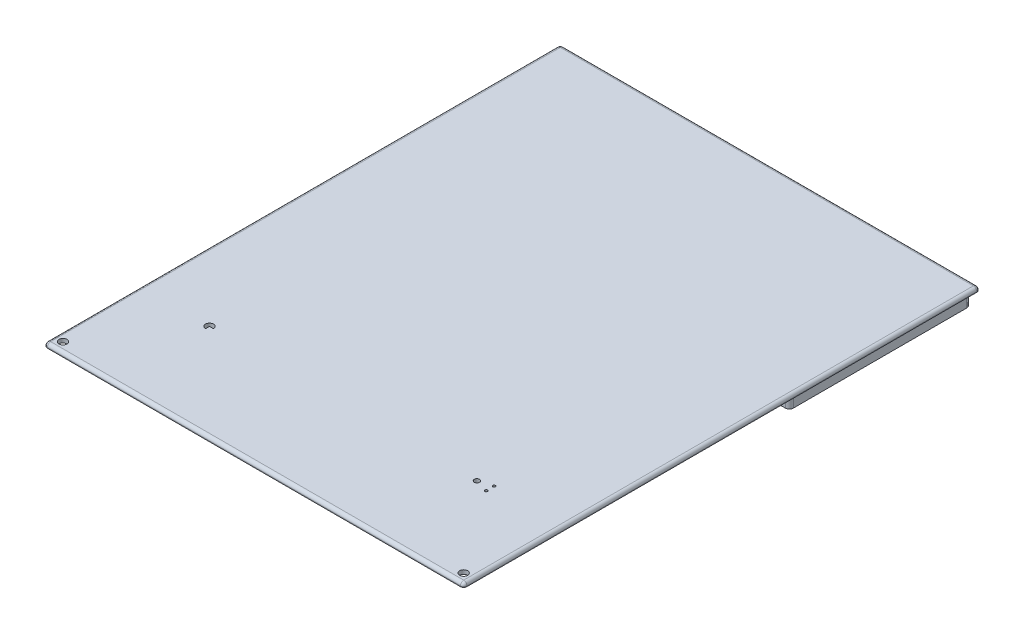
SolidWorks part; units mm, degrees
ref_plane "Front Plane" through (0, 0, 0) normal (0, 0, 1) x (1, 0, 0)
ref_plane "Top Plane" through (0, 0, 0) normal (0, 1, 0) x (1, 0, 0)
ref_plane "Right Plane" through (0, 0, 0) normal (1, 0, 0) x (0, 0, -1)
sketch "Sketch1" plane through (0, 0, 0) normal (0, 1, 0) x (1, 0, 0)
  line L0 (79.25, -36) -> (79.25, 36)
  line L1 (-78, -34.75) -> (78, -34.75)
  line L2 (-78, -34.75) -> (-78, 34.75)
  line L3 (-78, 34.75) -> (78, 34.75)
  line L4 (78, -34.75) -> (78, 34.75)
  line L5 (-78, -34.75) -> (78, 34.75) construction
  line L6 (-78, 34.75) -> (78, -34.75) construction
  line L7 (-79.25, 36) -> (79.25, 36)
  line L8 (-79.25, -36) -> (-79.25, 36)
  line L9 (-78, -36) -> (78, -36)
  line L10 (-78, -36) -> (-78, -86)
  line L11 (-78, -36) -> (78, -36)
  line L12 (-79.25, -36) -> (-79.25, -86)
  line L13 (-79.25, -86) -> (-79.25, -159)
  line L14 (79.25, -36) -> (79.25, -86)
  line L15 (78, -36) -> (78, -86)
  line L16 (-79.25, -36) -> (79.25, -36) construction
  line L17 (-78, -86) -> (-78, -100.5886)
  line L18 (79.25, -86) -> (79.25, -159)
  line L19 (78, -86) -> (78, -157.75)
  line L20 (79.25, -159) -> (-79.25, -159)
  line L21 (78, -159) -> (79.25, -159)
  line L22 (-78, -100.5886) -> (-78, -157.75)
  line L23 (-78, -157.75) -> (78, -157.75)
  line L24 (-78, -157.75) -> (78, -157.75) construction
  line L25 (0, -157.75) -> (0, -117.25)
  line L26 (-40, -117.25) -> (40, -117.25)
  line L27 (-34, -117.25) -> (34, -117.25)
  line L28 (-40, -117.25) -> (-34, -117.25) construction
  circle A0 centre (-37, -117.25) radius 3
  point P0 (0, 0)
  point P27 (0, -117.25)
  point P30 (0, -117.25)
  dimension "D1" = 156
  dimension "D2" = 69.5
  dimension "D4" = 50
  dimension "D5" = 195
  dimension "D6" = 1.25
  dimension "D7" = 40.5
  dimension "D8" = 80
  dimension "D9" = 68
  dimension "D3" = 1.25
sketch "Sketch2" plane through (0, 0, 0) normal (0, 1, 0) x (1, 0, 0)
  line L0 (-79.25, 36) -> (79.25, 36)
  line L1 (79.25, 36) -> (79.25, -159)
  line L2 (79.25, -159) -> (-79.25, -159)
  line L3 (-79.25, -159) -> (-79.25, 36)
extrude "Boss-Extrude1" add sketch "Sketch2" against normal blind 1.25
extrude "Boss-Extrude2" add sketch "Sketch1" along normal blind 105 contours L20 L18 L14 L0 L7 L8 L12 L13 L23 L22 L17 L10 L9 L15 L19 L4 L1 L2 L3 region at (78.9987, 0, 61)
sketch "Sketch4" plane through (0, 0, 0) normal (0, 1, 0) x (1, 0, 0)
  line L0 (-78, -157.75) -> (78, -157.75) construction
  line L1 (0, -157.75) -> (0, -117.75)
  line L2 (0, -5.0875) -> (0, 5.0875) construction
  line L3 (-34, -117.75) -> (34, -117.75)
  line L4 (-40.15, -117.75) -> (-39.575, -117.75)
  line L5 (-40.15, -117.75) -> (-39.575, -117.75) construction
  line L6 (34, -117.75) -> (34.575, -117.75) construction
  line L7 (-34.575, -117.75) -> (34.575, -117.75)
  line L8 (-34.575, -117.75) -> (-34, -117.75) construction
  line L9 (39.575, -117.75) -> (40.15, -117.75) construction
  line L10 (39.575, -117.75) -> (40.15, -117.75)
  circle A0 centre (-37.075, -117.75) radius 2.5
  circle A1 centre (37.075, -117.75) radius 2.5
  point P12 (0, -117.75)
  point P15 (0, -117.75)
  dimension "D1" = 40
  dimension "D2" = 68
  dimension "D3" = 80.3
extrude "Boss-Extrude3" add sketch "Sketch4" along normal blind 8 contours A0 | A1 region at (37.075, 0, 117.75) region at (-37.075, 0, 117.75)
fillet "Fillet2" radius 2 18 edges at (-78, 0, 0) (0, 0, -34.75) (78, 0, 0) (0, 0, 34.75) (0, 0, 36) (78, 0, 96.875) (0, 0, 157.75) (-78, 0, 96.875) (-37.075, 0, 115.25) (37.075, 0, 115.25) (78, 52.5, -34.75) (-78, 52.5, -34.75) (78, 52.5, 34.75) (-78, 52.5, 34.75) (-78, 52.5, 157.75) (78, 52.5, 157.75) (78, 52.5, 36) (-78, 52.5, 36)
sketch "Sketch5" plane through (0, 0, 36) normal (0, 0, 1) x (1, 0, 0)
  line L0 (-76, 105) -> (76, 105) construction
  line L2 (-76, 105) -> (-76, 2) construction
  line L3 (-58.75, 4.5) -> (58.75, 4.5)
  line L4 (-58.75, 4.5) -> (-58.75, 101.5)
  line L5 (-58.75, 101.5) -> (58.75, 101.5)
  line L6 (58.75, 4.5) -> (58.75, 101.5)
  line L7 (-58.75, 53) -> (58.75, 53)
  line L8 (-53.75, 101.5) -> (-53.75, 98)
  line L14 (-58.75, 98) -> (-53.75, 98)
  line L15 (0, 53) -> (0, 77.907)
  circle A0 centre (-53.75, 98) radius 1.55
  circle A1 centre (-53.75, 8) radius 1.55
  circle A2 centre (53.75, 8) radius 1.55
  circle A3 centre (53.75, 98) radius 1.55
  point P8 (0, 53.5)
  dimension "D1" = 97
  dimension "D2" = 117.5
  dimension "D3" = 17.25
  dimension "D4" = 3.5
  dimension "D5" = 5
  dimension "D6" = 3.5
extrude "Cut-Extrude1" cut sketch "Sketch5" against normal blind 8 contours L14 A0 L8 | L8 A0 L14 | A3 | A1 | A2 region at (-54.4078, 98.6578, 36) region at (-53.5307, 97.7807, 36) region at (-53.75, 8, 36) region at (53.75, 98, 36)
sketch "Sketch6" plane through (0, 0, 157.75) normal (0, 0, -1) x (-1, 0, 0)
  line L0 (-76, 2) -> (76, 2) construction
  line L1 (0, 2) -> (0, 22)
  line L2 (0, 5.0875) -> (0, -5.0875) construction
  circle A0 centre (0, 22) radius 8.25
  dimension "D1" = 20
extrude "Cut-Extrude2" cut sketch "Sketch6" against normal blind 8 contours A0 region at (-5.6686, 16.3314, 157.75)
sketch "Sketch8" plane through (-79.25, 0, 0) normal (-1, 0, 0) x (0, 0, 1)
  line L0 (159, 55) -> (116.5, 55)
  line L1 (159, -1.25) -> (159, 105) construction
  line L2 (116.5, 5) -> (116.5, 105)
  line L3 (159, 105) -> (-36, 105) construction
  line L4 (116.5, 55) -> (101.5, 55)
  line L5 (116.5, 55) -> (131.5, 55)
  line L7 (113, 58) -> (120, 58)
  line L8 (113, 58) -> (113, 72)
  line L9 (113, 72) -> (120, 72)
  line L10 (120, 58) -> (120, 72)
  line L11 (113, 58) -> (120, 72) construction
  line L12 (113, 72) -> (120, 58) construction
  circle A0 centre (101.5, 55) radius 3
  circle A1 centre (101.5, 65) radius 3
  circle A2 centre (101.5, 75) radius 3
  circle A3 centre (101.5, 85) radius 3
  circle A4 centre (131.5, 55) radius 3.75
  circle A5 centre (131.5, 75) radius 3.75
  point P9 (116.5, 55)
  point P13 (116.5, 65)
  dimension "D4" = 4
  dimension "D5" = 2
  dimension "D1" = 42.5
  dimension "D2" = 15
  dimension "D3" = 15
  dimension "D6" = 7
  dimension "D7" = 14
  dimension "D8" = 10
  dimension "D9" = 50
extrude "Cut-Extrude3" cut sketch "Sketch8" against normal blind 8 contours A0 | A2 | A3 | A1 | A5 | L8 L9 L10 L7 | A4 region at (-79.25, 55, 98.5849) region at (-79.25, 65, 101.5) region at (-79.25, 75, 101.5) region at (-79.25, 85, 101.5) region at (-79.25, 75, 131.5)
fillet "Fillet3" radius 1.25 4 edges at (0, -1.25, 159) (79.25, -1.25, 61.5) (0, -1.25, -36) (-79.25, -1.25, 61.5)
fillet "Fillet4" radius 1.25 8 edges at (-78.8839, -0.8839, 158.6339) (78.8839, -0.8839, 158.6339) (78.8839, -0.8839, -35.6339) (-78.8839, -0.8839, -35.6339) (-79.25, 52.5, 159) (79.25, 52.5, 159) (79.25, 52.5, -36) (-79.25, 52.5, -36)
sketch "Sketch11" plane through (79.25, 0, 0) normal (1, 0, 0) x (0, 0, -1)
  line L0 (-157.75, 105) -> (34.75, 0) construction
  line L1 (34.75, 105) -> (-157.75, 0)
  line L2 (87.175, 0) -> (-87.175, 0) construction
  line L4 (-111.5, 102.5) -> (-11.5, 102.5)
  line L5 (-111.5, 102.5) -> (-111.5, 2.5)
  line L6 (-111.5, 2.5) -> (-11.5, 2.5)
  line L7 (-11.5, 102.5) -> (-11.5, 2.5)
  line L8 (-111.5, 102.5) -> (-11.5, 2.5) construction
  line L9 (-111.5, 2.5) -> (-11.5, 102.5) construction
  line L10 (-99, 15) -> (-24, 15)
  line L11 (-99, 15) -> (-99, 90)
  line L12 (-99, 90) -> (-24, 90)
  line L13 (-24, 15) -> (-24, 90)
  line L14 (-99, 15) -> (-24, 90) construction
  line L15 (-99, 90) -> (-24, 15) construction
  circle A0 centre (-11.5, 102.5) radius 1.55
  circle A1 centre (-111.5, 102.5) radius 1.55
  circle A2 centre (-99, 90) radius 1.55
  circle A3 centre (-24, 90) radius 1.55
  circle A4 centre (-99, 15) radius 1.55
  circle A5 centre (-111.5, 2.5) radius 1.55
  circle A6 centre (-11.5, 2.5) radius 1.55
  circle A7 centre (-24, 15) radius 1.55
  point P9 (-61.5, 52.5)
  point P14 (-61.5, 52.5)
  dimension "D1" = 100
  dimension "D2" = 100
  dimension "D3" = 75
  dimension "D4" = 75
extrude "Cut-Extrude4" cut sketch "Sketch11" against normal blind 8 contours L7 A0 L4 | L4 A0 L7 | L13 A3 L12 | L12 A3 L13 | L6 A6 L7 | L5 A5 L6 | L6 A5 L5 | L11 A4 L10 | L10 A4 L11 | L10 A7 L13 | L13 A7 L10 | A1 | A2 | A6 region at (79.25, 101.8422, 12.1578) region at (79.25, 102.7193, 11.2807) region at (79.25, 2.2807, 11.2807) region at (79.25, 14.7807, 23.7807) region at (79.25, 15.6578, 24.6578) region at (79.25, 89.3422, 24.6578) region at (79.25, 90.2193, 23.7807) region at (79.25, 15.6578, 98.3422) region at (79.25, 14.7807, 99.2193) region at (79.25, 2.2807, 111.7193) region at (79.25, 3.1578, 110.8422)
sketch "Sketch12" plane through (0, 105, 0) normal (0, 1, 0) x (1, 0, 0)
  line L0 (0, -155.75) -> (0, -144.3132)
  line L1 (-78, -157.75) -> (-73, -157.75)
  line L2 (-78, -157.75) -> (-78, -152.75)
  line L3 (-78, -152.75) -> (-73, -152.75)
  line L4 (-73, -157.75) -> (-73, -152.75)
  line L5 (-76, -155.75) -> (76, -155.75) construction
  line L6 (0, -5.0875) -> (0, 5.0875) construction
  line L7 (78, -152.75) -> (73, -152.75)
  line L8 (73, -157.75) -> (73, -152.75)
  line L9 (78, -157.75) -> (73, -157.75)
  line L10 (78, -157.75) -> (78, -152.75)
  line M6 (76, -157.75) -> (-76, -157.75)
  arc M7 (-76, -157.75) -> (-78, -155.75) centre (-76, -155.75) cw
  line M8 (-78, -155.75) -> (-78, -38)
  line M12 (78, -38) -> (78, -155.75)
  arc M13 (78, -155.75) -> (76, -157.75) centre (76, -155.75) cw
  dimension "D1" = 5
  dimension "D2" = 5
extrude "Boss-Extrude5" add sketch "Sketch12" against normal up to surface (105 mm away) contours L8 L7 M6 M13 M12 | L4 L3 M6 M8 M7 region at (75.427, 105, 155.177) region at (-75.427, 105, 155.177) up to face at (0, 0, 96.875)
fillet "Fillet5" radius 1.25 14 edges at (78, 53.5, 152.75) (77.4142, 0.5858, 152.75) (74.5, 0, 152.75) (73, 0, 154.25) (73, 0.5858, 157.1642) (-73, 0, 154.25) (-73, 0.5858, 157.1642) (-74.5, 0, 152.75) (-77.4142, 0.5858, 152.75) (73, 53.5, 157.75) (73, 52.5, 152.75) (-73, 53.5, 157.75) (-78, 53.5, 152.75) (-73, 52.5, 152.75)
sketch "Sketch14" plane through (0, 105, 0) normal (0, 1, 0) x (1, 0, 0)
  line L0 (78, -38) -> (78, -151.5) construction
  line L1 (73.3661, -153.1161) -> (78, -153.1161)
  line L2 (73.3661, -153.1161) -> (73.3661, -157.75)
  line L3 (73.3661, -157.75) -> (78, -157.75)
  line L4 (78, -153.1161) -> (78, -157.75)
  line L5 (73.3661, -153.1161) -> (78, -157.75) construction
  line L6 (78, -157.75) -> (78.0536, -157.7607) construction
  line L7 (0, -157.75) -> (0, -147.0716)
  line L8 (-71.75, -157.75) -> (71.75, -157.75) construction
  line L9 (0, -58.4375) -> (0, 58.4375) construction
  arc A0 (74.25, -152.75) -> (73, -154) centre (74.25, -154) ccw construction
  circle A1 centre (75.6831, -155.4331) radius 1.525
  circle A2 centre (-75.6831, -155.4331) radius 1.525
extrude "Cut-Extrude5" cut sketch "Sketch14" against normal blind 8 contours A1 | A2 region at (75.6831, 105, 155.4331) region at (-75.6831, 105, 155.4331)
sketch "Sketch15" plane through (0, 105, 0) normal (0, 1, 0) x (1, 0, 0)
  line L16 (76, 33) -> (-76, 33)
  line L17 (-76.25, 32.75) -> (-76.25, -32.75)
  line L18 (-76, -33) -> (76, -33)
  line L19 (76.25, -32.75) -> (76.25, 32.75)
  line L20 (-77.5, 32.75) -> (-77.5, -32.75)
  line L21 (-76, -34.25) -> (76, -34.25)
  line L22 (77.5, -32.75) -> (77.5, 32.75)
  line L23 (76, 34.25) -> (-76, 34.25)
  line L24 (-77.5, 32.75) -> (-77.5, -32.75)
  line L25 (-76, -34.25) -> (76, -34.25)
  line L26 (77.5, -32.75) -> (77.5, 32.75)
  line L27 (76, 34.25) -> (-76, 34.25)
  arc A8 (78, 32.75) -> (76, 34.75) centre (76, 32.75) ccw construction
  arc A17 (-76, 33) -> (-76.25, 32.75) centre (-76, 32.75) ccw
  arc A18 (-76.25, -32.75) -> (-76, -33) centre (-76, -32.75) ccw
  arc A19 (76, -33) -> (76.25, -32.75) centre (76, -32.75) ccw
  arc A20 (76.25, 32.75) -> (76, 33) centre (76, 32.75) ccw
  arc A21 (-76, 34.25) -> (-77.5, 32.75) centre (-76, 32.75) ccw
  arc A22 (-77.5, -32.75) -> (-76, -34.25) centre (-76, -32.75) ccw
  arc A23 (76, -34.25) -> (77.5, -32.75) centre (76, -32.75) ccw
  arc A24 (77.5, 32.75) -> (76, 34.25) centre (76, 32.75) ccw
  arc A25 (-76, 34.25) -> (-77.5, 32.75) centre (-76, 32.75) ccw
  arc A26 (-77.5, -32.75) -> (-76, -34.25) centre (-76, -32.75) ccw
  arc A27 (76, -34.25) -> (77.5, -32.75) centre (76, -32.75) ccw
  arc A28 (77.5, 32.75) -> (76, 34.25) centre (76, 32.75) ccw
  point P15 (77.4142, 34.1642)
  dimension "D1" = 0.5
  dimension "D2" = 1.25
extrude "Boss-Extrude6" add sketch "Sketch15" against normal blind 5 separate body
sketch "Sketch19" plane through (0, 105, 0) normal (0, 1, 0) x (1, 0, 0)
  circle A2 centre (75.6831, -155.4331) radius 1.525
  circle A3 centre (75.6831, -155.4331) radius 1.525
  circle A5 centre (-75.6831, -155.4331) radius 1.525
  circle A6 centre (-75.6831, -155.4331) radius 1.525
  dimension "D1" = 0
  dimension "D2" = 0
extrude "Cut-Extrude10" cut sketch "Sketch19" along normal blind 176.5 and the other way blind 9
sketch "Sketch16" plane through (0, 105, 0) normal (0, 1, 0) x (1, 0, 0)
  line L8 (-79.25, 34.75) -> (-79.25, -157.75)
  line L9 (-78, -159) -> (78, -159)
  line L10 (79.25, -157.75) -> (79.25, 34.75)
  line L11 (78, 36) -> (-78, 36)
  line L12 (-79.25, 34.75) -> (-79.25, -157.75)
  line L13 (-78, -159) -> (78, -159)
  line L14 (79.25, -157.75) -> (79.25, 34.75)
  line L15 (78, 36) -> (-78, 36)
  arc A8 (-79.25, -157.75) -> (-78, -159) centre (-78, -157.75) ccw
  arc A9 (78, -159) -> (79.25, -157.75) centre (78, -157.75) ccw
  arc A10 (79.25, 34.75) -> (78, 36) centre (78, 34.75) ccw
  arc A11 (-78, 36) -> (-79.25, 34.75) centre (-78, 34.75) ccw
  arc A12 (-79.25, -157.75) -> (-78, -159) centre (-78, -157.75) ccw
  arc A13 (78, -159) -> (79.25, -157.75) centre (78, -157.75) ccw
  arc A14 (79.25, 34.75) -> (78, 36) centre (78, 34.75) ccw
  arc A15 (-78, 36) -> (-79.25, 34.75) centre (-78, 34.75) ccw
  dimension "D1" = 0
extrude "Boss-Extrude7" add sketch "Sketch16" along normal blind 1.5
sketch "Sketch17" plane through (0, 105, 0) normal (0, -1, 0) x (1, 0, 0)
  line L5 (97.501, -101.5148) -> (-116.8928, -101.5148)
  line L6 (97.501, -101.5148) -> (97.501, 210.2358)
  line L7 (97.501, 210.2358) -> (-116.8928, 210.2358)
  line L8 (78, -32.75) -> (78, 32.75)
  line L9 (76, 34.75) -> (-76, 34.75)
  line L10 (-78, 32.75) -> (-78, -32.75)
  line L11 (-76, -34.75) -> (76, -34.75)
  line L12 (78, -32.75) -> (78, 32.75)
  line L13 (76, 34.75) -> (-76, 34.75)
  line L14 (-78, 32.75) -> (-78, -32.75)
  line L15 (-76, -34.75) -> (76, -34.75)
  line L16 (-116.8928, -101.5148) -> (-116.8928, 210.2358)
  line L17 (97.501, -101.5148) -> (-116.8928, 210.2358) construction
  line L18 (97.501, 210.2358) -> (-116.8928, -101.5148) construction
  arc A8 (78, 32.75) -> (76, 34.75) centre (76, 32.75) ccw
  arc A9 (-76, 34.75) -> (-78, 32.75) centre (-76, 32.75) ccw
  arc A10 (-78, -32.75) -> (-76, -34.75) centre (-76, -32.75) ccw
  arc A11 (76, -34.75) -> (78, -32.75) centre (76, -32.75) ccw
  arc A12 (78, 32.75) -> (76, 34.75) centre (76, 32.75) ccw
  arc A13 (-76, 34.75) -> (-78, 32.75) centre (-76, 32.75) ccw
  arc A14 (-78, -32.75) -> (-76, -34.75) centre (-76, -32.75) ccw
  arc A15 (76, -34.75) -> (78, -32.75) centre (76, -32.75) ccw
  point P2 (-9.6959, 54.3605)
  dimension "D1" = 0
extrude "Cut-Extrude6" cut sketch "Sketch17" along normal blind 142.5
sketch "Sketch18" plane through (0, 100, 0) normal (0, -1, 0) x (1, 0, 0)
  line L1 (-421.9306, -105.0953) -> (421.9306, -105.0953)
  line L2 (-421.9306, -105.0953) -> (-421.9306, 105.0953)
  line L3 (-421.9306, 105.0953) -> (421.9306, 105.0953)
  line L4 (421.9306, -105.0953) -> (421.9306, 105.0953)
  line L5 (-421.9306, -105.0953) -> (421.9306, 105.0953) construction
  line L6 (-421.9306, 105.0953) -> (421.9306, -105.0953) construction
  point P0 (0, 0)
extrude "Cut-Extrude7" cut sketch "Sketch18" along normal blind 211.5
fillet "Fillet6" radius 1.25 8 edges at (0, 106.5, -36) (78.8839, 106.5, -35.6339) (79.25, 106.5, 61.5) (78.8839, 106.5, 158.6339) (0, 106.5, 159) (-78.8839, 106.5, 158.6339) (-79.25, 106.5, 61.5) (-78.8839, 106.5, -35.6339)
sketch "Sketch21" plane through (0, 106.5, 0) normal (0, 1, 0) x (1, 0, 0)
  line L0 (-78.8839, -158.6339) -> (-75.6807, -155.4307)
  line L1 (0, -159) -> (0, -145.5027)
  line L2 (78, -159) -> (-78, -159) construction
  line L3 (0, -3.575) -> (0, 3.575) construction
  arc A0 (-79.25, -157.75) -> (-78, -159) centre (-78, -157.75) ccw construction
  circle A1 centre (-75.6807, -155.4307) radius 1.525
  circle A2 centre (75.6807, -155.4307) radius 1.525
  dimension "D1" = 4.53
extrude "Cut-Extrude11" cut sketch "Sketch21" against normal blind 46.5 contours A1 | A2
sketch "Sketch22" plane through (0, 106.5, 0) normal (0, 1, 0) x (1, 0, 0)
  line L0 (53, -122.75) -> (-53, -122.75)
  line L1 (-78, -157.75) -> (-53, -157.75)
  line L2 (-78, -157.75) -> (-78, -122.75)
  line L3 (-78, -122.75) -> (-53, -122.75)
  line L4 (-53, -157.75) -> (-53, -122.75)
  line L6 (53, -124.25) -> (53, -121.25)
  line L7 (53, -122.75) -> (48, -122.75)
  circle A0 centre (-53, -122.75) radius 1.525
  circle A1 centre (53, -121.25) radius 0.5
  circle A2 centre (53, -124.25) radius 0.5
  circle A3 centre (48, -122.75) radius 1
  point P9 (0, -122.75)
  point P11 (53, -122.75)
  dimension "D3" = 3
  dimension "D4" = 5
  dimension "D1" = 25
  dimension "D2" = 35
extrude "Cut-Extrude12" cut sketch "Sketch22" against normal blind 46.5 contours L3 A0 L4 | L4 A0 L3 | A2 | A1 | L7 A3 L0 | L0 A3 L7 region at (-53, 106.5, 122.1028) region at (48, 106.5, 123.1744) region at (48, 106.5, 122.3256) region at (53.3436, 106.5, 123.9064) region at (52.6564, 106.5, 120.9064) region at (-53.6472, 106.5, 123.3972)
